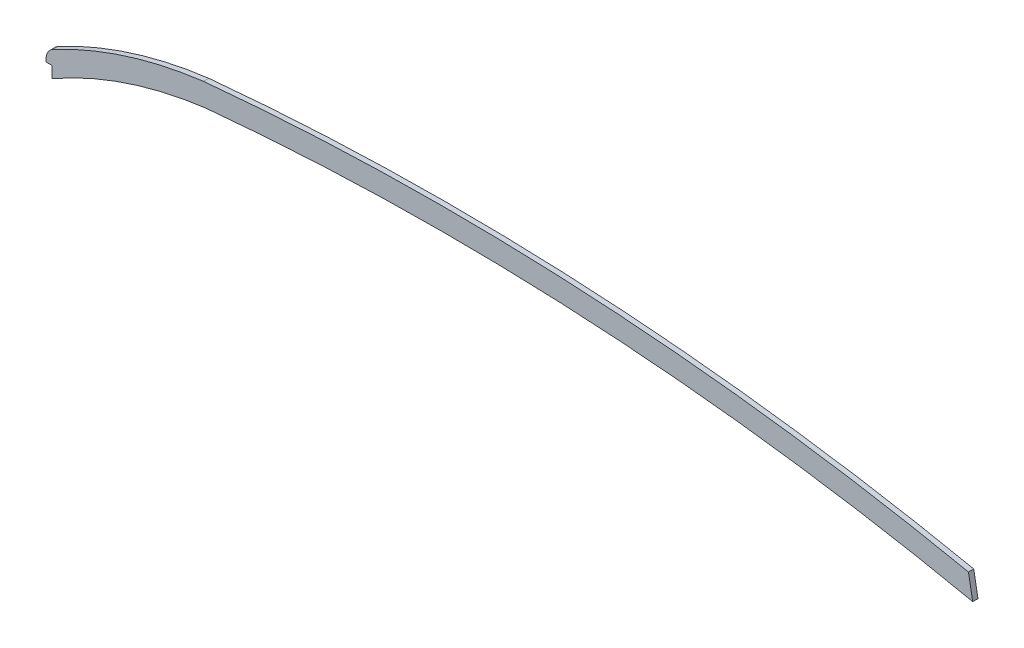
SolidWorks part; units mm, degrees
material "Balsa"
ref_plane "Front Plane" through (0, 0, 0) normal (0, 0, 1) x (1, 0, 0)
ref_plane "Top Plane" through (0, 0, 0) normal (0, 1, 0) x (1, 0, 0)
ref_plane "Right Plane" through (0, 0, 0) normal (1, 0, 0) x (0, 0, -1)
sketch "Sketch1" plane through (0, 0, 0) normal (0, 0, 1) x (1, 0, 0)
  line L0 (0, 101.6) -> (0, 100.0553)
  line L1 (0, -1.7463) -> (0, 1.7463) construction
  line L2 (0, 86.36) -> (8.1082, 86.36) construction
  line L3 (3.7499, 106.3536) -> (3.7499, -82.5359) construction
  line L4 (8.1082, 101.6) -> (0, 101.6) construction
  line L6 (3.7499, 93.1973) -> (0, 91.0322) construction
  line L7 (0, 99.5163) -> (0, 88.039) construction
  line L8 (558.2295, 97.6273) -> (555.6382, 111.8229)
  line L9 (0, 91.0322) -> (0, 86.36) construction
  line L10 (3.7499, 93.1973) -> (3.7499, 100.0553)
  line L11 (3.7499, 100.0553) -> (0, 97.8902) construction
  line L12 (0, 97.8902) -> (0, 91.0322) construction
  line L13 (3.7499, 100.0553) -> (0, 100.0553)
  line L14 (0, 100.0553) -> (0, 97.8902) construction
  line L26 (196.8609, -116.7457) -> (197.4984, -131.9724) construction
  line L28 (193.6887, -116.8786) -> (194.3262, -132.1052) construction
  line L32 (197.4984, -131.9724) -> (194.3262, -132.1052) construction
  line L41 (194.3262, -132.1052) -> (196.8609, -116.7457) construction
  line L42 (195.5936, -124.4255) -> (184.9758, 129.1656) construction
  line L70 (196.8609, -116.7457) -> (193.6887, -116.8786)
  line L72 (197.4984, -131.9724) -> (194.3262, -132.1052)
  line L74 (193.6887, -116.8786) -> (194.3262, -132.1052)
  line L78 (196.8609, -116.7457) -> (197.4984, -131.9724)
  line L79 (196.8609, -116.7457) -> (193.6887, -116.8786) construction
  arc A0 (4.3005, 108.7585) -> (94.8544, 137.376) centre (127, -121.92) cw
  arc A1 (4.3005, 108.7585) -> (0, 101.6) centre (8.1082, 101.6) ccw
  arc A2 (3.7499, 93.1973) -> (0, 86.36) centre (8.1082, 86.36) ccw construction
  arc A3 (94.8544, 137.376) -> (555.6382, 111.8229) centre (240.8652, -1397) cw
  arc A4 (3.7499, 93.1973) -> (96.3112, 124.0967) centre (127, -121.92) cw
  arc A5 (96.3112, 124.0967) -> (184.9758, 129.9274) centre (240.8652, -1397) cw
  arc A6 (10.5733, 96.9655) -> (96.3112, 124.0967) centre (127, -121.92) cw construction
  arc A7 (94.4927, 137.3434) -> (3.7499, 106.3536) centre (112.883, -64.8553) ccw construction
  arc A8 (96.3112, 124.0967) -> (552.9103, 98.7469) centre (240.8652, -1397) cw construction
  arc A9 (4.3005, 108.7585) -> (94.8544, 137.376) centre (127, -121.92) cw construction
  arc A11 (94.8544, 137.376) -> (555.6382, 111.8229) centre (240.8652, -1397) cw construction
  arc A13 (556.7512, 105.7321) -> (99.1899, 122.2822) centre (270.5046, -1474.7614) ccw construction
  arc A18 (184.9758, 129.9274) -> (275.6985, 130.5528) centre (240.8652, -1397) cw
  arc A21 (275.6985, 130.5528) -> (558.2295, 97.6273) centre (240.8652, -1397) cw
  spline S0 degree 3 poles (981.3177, 1818.2675) (1139.722, 204.4849) (873.2182, 1.0169) (565.628, -88.9106) (559.2919, -90.7077) (-121.8164, -278.7114) (-929.5333, 36.0269) (-1233.6865, -867.5095) knots -11.664502 -11.664502 -11.664502 -11.664502 0.25 0.25 0.5 0.5 27.071012 27.071012 27.071012 27.071012 only from (590.8643, -81.3536) to (514.7143, -102.4537) construction
  spline S1 degree 3 poles (1062.5522, -1662.3274) (1783.386, 752.2598) (1192.007, 51.9761) (480.6823, -110.4688) (472.1454, -112.3347) (455.0337, -115.879) (446.4591, -117.5582) (433.5613, -119.8984) (429.2558, -120.648) (422.7903, -121.7356) (420.6337, -122.0915) (417.3979, -122.6188) (416.3191, -122.7935) (329.7173, -136.7537) (244.3749, -151.8452) (-150.7518, 1789.6158) knots -20.37019 -20.37019 -20.37019 -20.37019 0.25 0.25 0.5 0.5 0.75 0.75 0.875 0.875 0.9375 0.9375 0.96875 0.96875 3.445896 3.445896 3.445896 3.445896 only from (514.7143, -102.4537) to (412.003, -123.4859) construction
  spline S2 degree 3 poles (-1526.2092, 975.8893) (-966.7298, 244.4948) (-373.5074, -121.9571) (226.7788, -133.168) (266.5142, -132.8729) (279.7628, -132.6016) (299.6408, -131.9345) (306.2677, -131.6688) (319.5231, -131.0505) (326.1536, -130.6977) (943.6584, -93.7895) (1501.3881, 309.0053) (2017.121, 1001.2295) knots -5.168103 -5.168103 -5.168103 -5.168103 0.25 0.5 0.5 0.625 0.625 0.6875 0.6875 0.75 0.75 6.511417 6.511417 6.511417 6.511417 only from (94.4926, -125.8525) to (412.003, -123.4859) construction
  spline S3 degree 3 poles (82.8406, 1879.826) (-241.5287, 509.6599) (-195.4311, -0.6421) (32.0968, -110.0953) (39.5136, -113.1375) (50.922, -117.0433) (54.7721, -118.2354) (60.6197, -119.8556) (62.5829, -120.3681) (66.5243, -121.3341) (68.5001, -121.787) (343.1899, -180.4478) (711.1357, 326.3263) (1193.75, 1513.3939) knots -7.368418 -7.368418 -7.368418 -7.368418 0.25 0.25 0.5 0.5 0.625 0.625 0.6875 0.6875 0.75 0.75 9.354609 9.354609 9.354609 9.354609 only from (3.7499, -94.8626) to (94.4926, -125.8525) construction
  spline S6 degree 3 poles (590.8643, -81.3536) (584.5771, -83.3154) (578.2709, -85.2143) (565.628, -88.9106) (559.2919, -90.7077) (540.2459, -95.9648) (527.5015, -99.2922) (514.7143, -102.4537) knots 0 0 0 0 0.25 0.25 0.5 0.5 1 1 1 1 construction
  spline S7 degree 3 poles (514.7143, -102.4537) (506.2284, -104.5517) (497.724, -106.577) (480.6823, -110.4688) (472.1454, -112.3347) (455.0337, -115.879) (446.4591, -117.5582) (433.5613, -119.8984) (429.2558, -120.648) (422.7903, -121.7356) (420.6337, -122.0915) (417.3979, -122.6188) (416.3191, -122.7935) (414.1613, -123.1413) (413.0825, -123.3155) (412.003, -123.4859) knots 0 0 0 0 0.25 0.25 0.5 0.5 0.75 0.75 0.875 0.875 0.9375 0.9375 0.96875 0.96875 1 1 1 1 construction
  spline S8 degree 3 poles (94.4926, -125.8525) (120.9278, -128.4258) (173.8258, -132.179) (226.7788, -133.168) (266.5142, -132.8729) (279.7628, -132.6016) (299.6408, -131.9345) (306.2677, -131.6688) (319.5231, -131.0505) (326.1536, -130.6977) (359.2877, -128.7173) (385.6949, -126.4433) (412.003, -123.4859) knots 0 0 0 0 0.25 0.5 0.5 0.625 0.625 0.6875 0.6875 0.75 0.75 1 1 1 1 construction
  spline S9 degree 3 poles (3.7499, -94.8626) (10.597, -99.2271) (17.6385, -103.1401) (32.0968, -110.0953) (39.5136, -113.1375) (50.922, -117.0433) (54.7721, -118.2354) (60.6197, -119.8556) (62.5829, -120.3681) (66.5243, -121.3341) (68.5001, -121.787) (78.4043, -123.9021) (86.408, -125.1172) (94.4926, -125.8525) knots 0 0 0 0 0.25 0.25 0.5 0.5 0.625 0.625 0.6875 0.6875 0.75 0.75 1 1 1 1 construction
  spline S15 degree 3 poles (587.4426, -62.5747) (587.1827, -61.1511) (586.6535, -58.2526) (585.7873, -53.5174) (584.8512, -48.394) (583.8406, -42.8532) (582.7565, -36.9006) (581.5991, -30.5376) (580.1295, -22.4773) (578.3524, -12.6853) (576.2505, -1.1976) (574.1192, 10.4518) (571.9272, 22.5233) (569.819, 34.0829) (567.7342, 45.5019) (565.8232, 55.9911) (564.3841, 63.8754) (563.4512, 68.9947) (562.9209, 71.9076) (562.4102, 74.7138) (561.9192, 77.4122) (561.4478, 80.0018) (560.9959, 82.4822) (560.5637, 84.8528) (560.1512, 87.1138) (559.7582, 89.2651) (559.385, 91.3073) (559.0312, 93.2414) (558.6975, 95.0661) (558.3822, 96.7905) (558.1867, 97.8615) (558.0896, 98.3936) knots 0 0 0 0 0.031687 0.064515 0.098497 0.133644 0.169967 0.207478 0.246191 0.30842 0.370332 0.432609 0.495165 0.563925 0.620591 0.686243 0.746551 0.766006 0.785258 0.804303 0.823142 0.841774 0.860197 0.878411 0.896416 0.91421 0.931793 0.949164 0.966322 0.983268 1 1 1 1 construction
  point P19 (96.1383, 124.0967)
  point P38 (184.9758, 129.9274)
  point P39 (185.0244, 129.9292)
  point P43 (274.0348, 130.5899)
  point P44 (275.6985, 130.5528)
  point P45 (275.8358, 130.5497)
  dimension "D4" = 8.1082
  dimension "D2" = 127
  dimension "D8" = 1397
  dimension "D9" = 30
  dimension "D1" = 15.24
  dimension "D3" = 8.1082
  dimension "D5" = 8.1082
  dimension "D6" = 101.6
  dimension "D7" = 121.92
  dimension "D10" = 6.858
  dimension "D11" = 3.7499
extrude "Boss-Extrude1" add sketch "Sketch1" against normal blind 3.175 contours A21 L8 A3 A0 A1 L0 L13 L10 A4 A5 A18 region at (5.963, 102.8887, 0)
equation "\"slotwidth\"=0.167708"
